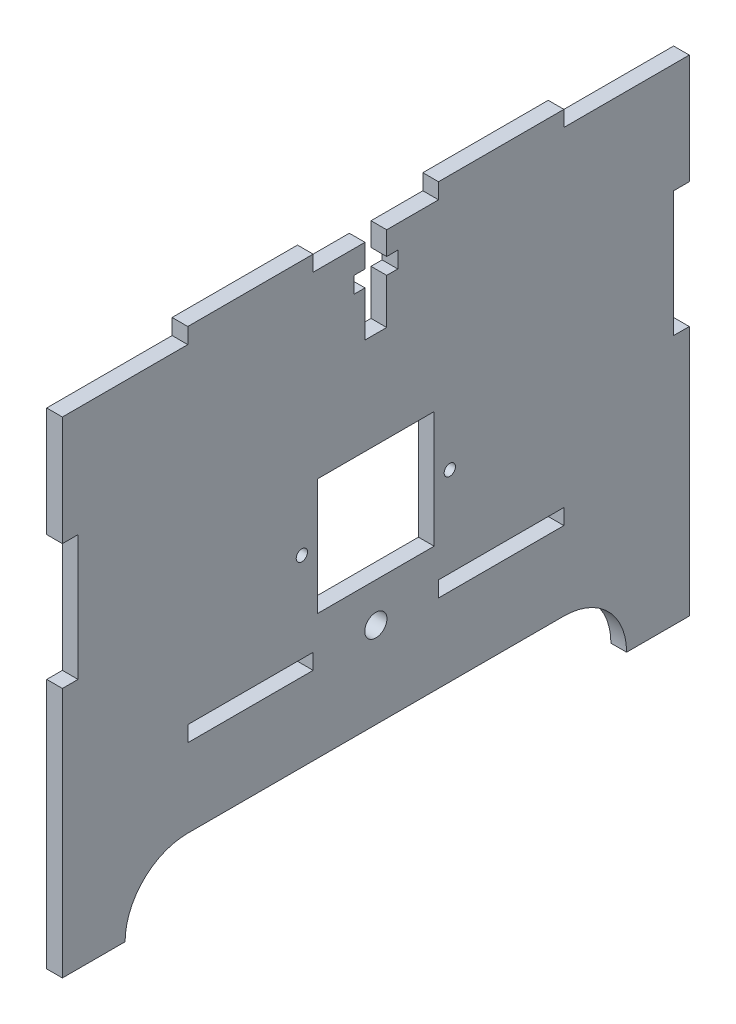
SolidWorks part; units mm, degrees
ref_plane "Front Plane" through (0, 0, 0) normal (0, 0, 1) x (1, 0, 0)
ref_plane "Top Plane" through (0, 0, 0) normal (0, 1, 0) x (1, 0, 0)
ref_plane "Right Plane" through (0, 0, 0) normal (1, 0, 0) x (0, 0, -1)
sketch "Sketch1" plane through (0, 0, 0) normal (1, 0, 0) x (0, 0, -1)
  line L1 (-63.5, 50.8) -> (63.5, 50.8)
  line L2 (-63.5, 50.8) -> (-63.5, -50.8)
  line L3 (-63.5, -50.8) -> (63.5, -50.8)
  line L4 (63.5, 50.8) -> (63.5, -50.8)
  line L5 (-63.5, 50.8) -> (63.5, -50.8) construction
  line L6 (-63.5, -50.8) -> (63.5, 50.8) construction
  point P0 (0, 0)
  dimension "D1" = 127
  dimension "D2" = 101.6
extrude "Boss-Extrude1" add sketch "Sketch1" along normal blind 3.175
sketch "Sketch2" plane through (3.175, 0, 0) normal (1, 0, 0) x (0, 0, -1)
  line L1 (-63.5, 50.8) -> (-38.1, 50.8)
  line L2 (-63.5, 50.8) -> (-63.5, 47.625)
  line L3 (-63.5, 47.625) -> (-38.1, 47.625)
  line L4 (-38.1, 50.8) -> (-38.1, 47.625)
  dimension "D1" = 25.4
  dimension "D2" = 3.175
extrude "Cut-Extrude1" cut sketch "Sketch2" against normal blind 6.35
pattern_linear "LPattern1" count 3 spacing 50.8 along (0, 0, -1) of "Cut-Extrude1"
sketch "Sketch5" plane through (3.175, 0, 0) normal (1, 0, 0) x (0, 0, -1)
  line L0 (-38.1, -50.8) -> (38.1, -50.8) construction
  line L1 (-63.5, -50.8) -> (63.5, -50.8) construction
  line L2 (-38.1, -38.1) -> (38.1, -38.1)
  line L3 (-38.1, -63.5) -> (38.1, -63.5)
  arc A0 (-38.1, -38.1) -> (-38.1, -63.5) centre (-38.1, -50.8) ccw
  arc A1 (38.1, -63.5) -> (38.1, -38.1) centre (38.1, -50.8) ccw
  point P4 (0, -50.8)
  dimension "D2" = 12.7
  dimension "D1" = 76.2
extrude "Cut-Extrude4" cut sketch "Sketch5" against normal blind 6.35
sketch "Sketch8" plane through (3.175, 0, 0) normal (1, 0, 0) x (0, 0, -1)
  line L0 (63.5, -50.8) -> (63.5, 47.625) construction
  line L1 (63.5, 25.4) -> (60.325, 25.4)
  line L2 (63.5, 25.4) -> (63.5, 0)
  line L3 (63.5, 0) -> (60.325, 0)
  line L4 (60.325, 25.4) -> (60.325, 0)
  line L5 (38.1, 50.8) -> (12.7, 50.8) construction
  dimension "D1" = 25.4
  dimension "D2" = 25.4
  dimension "D3" = 3.175
extrude "Cut-Extrude6" cut sketch "Sketch8" against normal blind 6.35
ref_plane "Plane1" through (0, 0, 0) normal (0, 0, 1) x (1, 0, 0)
sketch "Sketch9" plane through (0, 0, 0) normal (-1, 0, 0) x (0, 0, 1)
  line L0 (-63.5, -50.8) -> (-63.5, 0) construction
  line L1 (-38.1, -19.05) -> (-12.7, -19.05)
  line L2 (-38.1, -19.05) -> (-38.1, -22.225)
  line L3 (-38.1, -22.225) -> (-12.7, -22.225)
  line L4 (-12.7, -19.05) -> (-12.7, -22.225)
  line L5 (-38.1, 50.8) -> (-12.7, 50.8) construction
  point P6 (-25.4, 50.8)
  dimension "D1" = 25.4
  dimension "D2" = 3.175
  dimension "D3" = 25.4
  dimension "D4" = 69.85
extrude "Cut-Extrude7" cut sketch "Sketch9" against normal blind 6.35
pattern_linear "LPattern6" count 2 spacing 50.8 along (0, 0, 1) of "Cut-Extrude7"
sketch "Sketch16" plane through (0, 0, 0) normal (-1, 0, 0) x (0, 0, 1)
  line L0 (12.7, 47.625) -> (-12.7, 47.625) construction
  line L1 (-2.1971, 47.625) -> (2.1971, 47.625)
  line L2 (-2.1971, 47.625) -> (-2.1971, 30.48)
  line L3 (-2.1971, 30.48) -> (2.1971, 30.48)
  line L4 (2.1971, 47.625) -> (2.1971, 30.48)
  line L5 (-12.7, 47.625) -> (-12.7, 50.8) construction
  line L7 (-4.445, 42.926) -> (4.445, 42.926)
  line L8 (-4.445, 42.926) -> (-4.445, 39.624)
  line L9 (-4.445, 39.624) -> (4.445, 39.624)
  line L10 (4.445, 42.926) -> (4.445, 39.624)
  point P6 (0, 30.48)
  point P13 (0, 42.926)
  point P14 (4.445, 41.275)
  dimension "D1" = 4.3942
  dimension "D2" = 17.145
  dimension "D3" = 12.7
  dimension "D4" = 3.302
  dimension "D5" = 8.89
  dimension "D6" = 12.7
  dimension "D7" = 6.35
extrude "Cut-Extrude14" cut sketch "Sketch16" against normal blind 6.35 contours L7 L10 L9 L8 | L1 L4 L3 L2
hole_wizard "#8 Clearance Hole1" positions "Sketch18" profile "Sketch17" hole size "#8" standard "ANSI Inch"
sketch "Sketch18" plane through (0, 0, 0) normal (-1, 0, 0) x (0, 0, 1)
  line L3 (-12.7, -22.225) -> (-12.7, -19.05) construction
  line L4 (38.1, -19.05) -> (12.7, -19.05) construction
  point P0 (0, -20.6375)
  point P16 (-12.7, -20.6375)
  dimension "D1" = 12.7
  dimension "D2" = 1.5875
sketch "Sketch17" plane through (0, -20.6375, 0) normal (0, 1, 0) x (0, 0, 1)
  line L0 (0, 0) -> (0, 11.5107)
  line L1 (0, 11.5107) -> (2.2479, 10.16)
  line L2 (2.2479, 10.16) -> (2.2479, 0)
  line L5 (2.2479, 0) -> (0, 0)
  line L10 (0, 11.5107) -> (-2.2479, 10.16) construction
  line L11 (0, -6.35) -> (0, 107.95) construction
  dimension "Hole Dia." = 4.4958
  dimension "Hole Depth" = 10.16
  dimension "Drill Angle" = 118
sketch "Sketch19" plane through (0, 0, 0) normal (-1, 0, 0) x (0, 0, 1)
  line L0 (-49.53, 42.545) -> (-11.43, 42.545) construction
  line L1 (-49.53, 43.815) -> (-11.43, 43.815)
  line L2 (-49.53, 41.275) -> (-11.43, 41.275)
  line L3 (-38.1, 50.8) -> (-38.1, 47.625) construction
  line L4 (-2.1971, 47.625) -> (-12.7, 47.625) construction
  arc A0 (-49.53, 43.815) -> (-49.53, 41.275) centre (-49.53, 42.545) ccw
  arc A1 (-11.43, 41.275) -> (-11.43, 43.815) centre (-11.43, 42.545) ccw
  point P2 (-30.48, 42.545)
  point P7 (-30.48, 43.815)
  dimension "D2" = 1.27
  dimension "D1" = 38.1
  dimension "D3" = 7.62
  dimension "D4" = 3.81
extrude "Cut-Extrude15" [suppressed] cut sketch "Sketch19" against normal blind 6.35
mirror "Mirror2" [suppressed] about plane through (0, 0, 0) normal (0, 0, 1)
pattern_linear "LPattern7" [suppressed] count 5 spacing 5.08 of bodies 127
sketch "Sketch20" plane through (0, 0, 0) normal (-1, 0, 0) x (0, 0, 1)
  line L0 (-63.5, -50.8) -> (-63.5, 0) construction
  line L1 (-11.811, 10.922) -> (11.811, 10.922)
  line L2 (-11.811, 10.922) -> (-11.811, -12.7)
  line L3 (-11.811, -12.7) -> (11.811, -12.7)
  line L4 (11.811, 10.922) -> (11.811, -12.7)
  line L5 (38.1, -19.05) -> (12.7, -19.05) construction
  circle A0 centre (-14.986, -0.889) radius 1.143
  circle A1 centre (14.986, -0.889) radius 1.143
  point P4 (0, -12.7)
  point P11 (0, 10.922)
  point P12 (-11.811, -0.889)
  point P15 (11.811, -0.889)
  dimension "D6" = 2.286
  dimension "D7" = 2.286
  dimension "D8" = 14.986
  dimension "D1" = 23.622
  dimension "D2" = 23.622
  dimension "D3" = 63.5
  dimension "D4" = 6.35
  dimension "D5" = 14.986
extrude "Cut-Extrude16" cut sketch "Sketch20" against normal blind 10.16
mirror "Mirror3" about plane through (0, 0, 0) normal (0, 0, 1) of "Cut-Extrude6"
